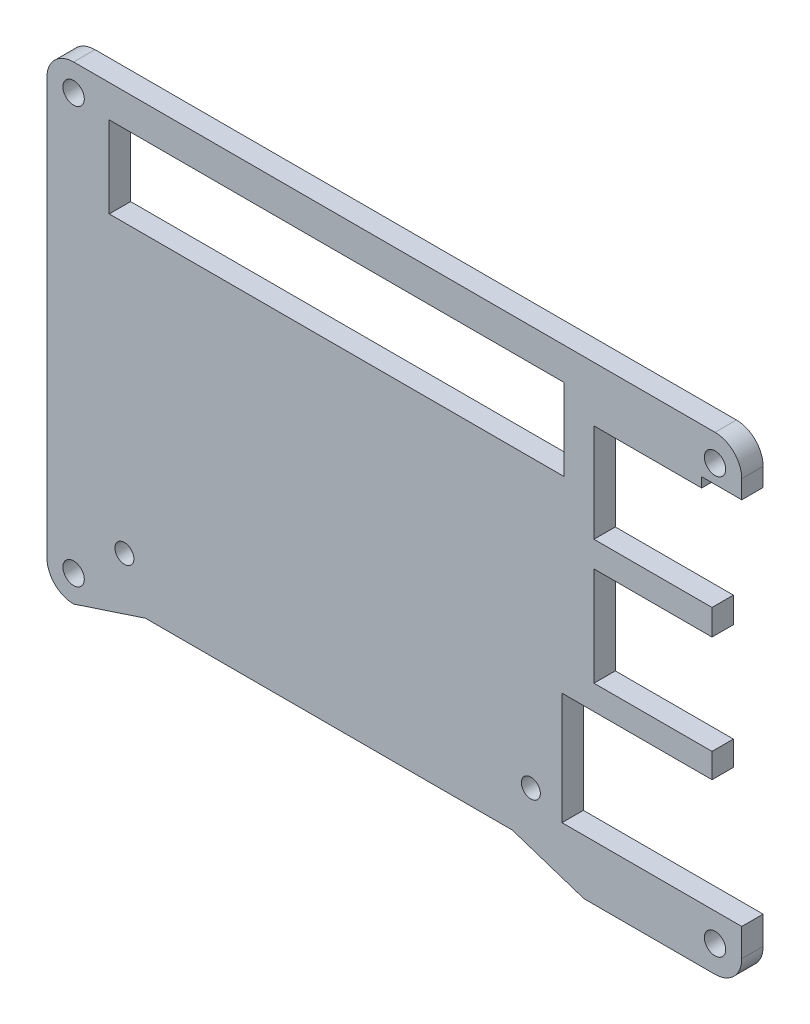
SolidWorks part; units mm, degrees
ref_plane "Front Plane" through (0, 0, 0) normal (0, 0, 1) x (1, 0, 0)
ref_plane "Top Plane" through (0, 0, 0) normal (0, 1, 0) x (1, 0, 0)
ref_plane "Right Plane" through (0, 0, 0) normal (1, 0, 0) x (0, 0, -1)
sketch "Sketch1" plane through (0, 0, 0) normal (0, 0, 1) x (1, 0, 0)
  line L1 (61.2149, 24.0683) -> (61.2149, 26.6839) construction
  line L2 (57.4049, 30.5077) -> (-34.0849, 30.5077) construction
  line L5 (56.975, 4.9979) -> (56.975, 8.6582) construction
  line L9 (56.975, -12.628) -> (56.975, -9.1218) construction
  line L10 (35.575, -12.628) -> (56.975, -12.628) construction
  line L11 (35.575, -28.6278) -> (35.575, -12.628) construction
  line L12 (61.2149, -28.6278) -> (35.575, -28.6278) construction
  line L13 (61.2149, -32.6134) -> (61.2149, -28.6278) construction
  line L14 (38.7143, -36.451) -> (57.405, -36.451) construction
  line L15 (28.4743, -33.0844) -> (38.7143, -36.451) construction
  line L16 (-23.8449, -33.0844) -> (28.4743, -33.0844) construction
  line L17 (-34.0849, -36.451) -> (-23.8449, -33.0844) construction
  line L18 (-37.8949, 26.6977) -> (-37.8949, -32.641) construction
  line L19 (61.2149, 24.0683) -> (40.1348, 24.0683)
  line L20 (61.2149, 24.0683) -> (61.2149, 26.6839)
  line L21 (57.4049, 30.5077) -> (-34.0849, 30.5077)
  line L22 (40.1348, 24.0683) -> (40.1348, 8.6582)
  line L23 (40.1348, 8.6582) -> (56.975, 8.6582)
  line L24 (56.975, 4.9979) -> (56.975, 8.6582)
  line L25 (56.975, 4.9979) -> (40.1348, 4.9979)
  line L26 (40.1348, 4.9979) -> (40.1348, -9.1218)
  line L27 (40.1348, -9.1218) -> (56.975, -9.1218)
  line L28 (56.975, -12.628) -> (56.975, -9.1218)
  line L29 (35.575, -12.628) -> (56.975, -12.628)
  line L30 (35.575, -28.6278) -> (35.575, -12.628)
  line L31 (61.2149, -28.6278) -> (35.575, -28.6278)
  line L32 (61.2149, -32.6134) -> (61.2149, -28.6278)
  line L33 (38.7143, -36.451) -> (57.405, -36.451)
  line L34 (28.4743, -33.0844) -> (38.7143, -36.451)
  line L35 (-23.8449, -33.0844) -> (28.4743, -33.0844)
  line L36 (-34.0849, -36.451) -> (-23.8449, -33.0844)
  line L37 (-37.8949, 26.6977) -> (-37.8949, -32.641)
  line L38 (-23.4169, -23.6989) -> (-23.4169, 9.8012) construction
  line L39 (-29.0049, 25.897) -> (31.6883, 25.897)
  line L40 (-29.0049, 25.897) -> (-29.0049, 18.087)
  line L41 (-29.0049, 18.087) -> (31.6883, 18.087)
  line L42 (31.6883, 25.897) -> (31.6883, 18.087)
  line L43 (-29.0049, 9.8012) -> (-23.4169, 9.8012)
  line L44 (-29.0049, 9.8012) -> (-29.0049, -13.5668)
  line L45 (-29.0049, -13.5668) -> (-23.4169, -13.5668)
  line L46 (-23.4169, 9.8012) -> (-23.4169, -13.5668)
  line L47 (-29.0049, 9.2932) -> (-23.4169, 9.2932)
  line L50 (13.845, -8.3602) -> (19.2484, -8.3602)
  line L51 (13.845, -8.3602) -> (13.845, -30.9668)
  line L52 (13.845, -30.9668) -> (19.2484, -30.9668)
  line L53 (19.2484, -8.3602) -> (19.2484, -30.9668)
  arc A0 (61.2149, 26.6839) -> (57.4049, 30.5077) centre (57.4049, 26.6977) ccw construction
  arc A2 (57.405, -36.451) -> (61.2149, -32.6134) centre (57.405, -32.641) ccw construction
  arc A3 (-37.8949, -32.641) -> (-34.0849, -36.451) centre (-34.0849, -32.641) ccw construction
  arc A4 (-34.0849, 30.5077) -> (-37.8949, 26.6977) centre (-34.0849, 26.6977) ccw construction
  arc A7 (61.2149, 26.6839) -> (57.4049, 30.5077) centre (57.4049, 26.6977) ccw
  circle A8 centre (57.405, -32.641) radius 1.524
  arc A9 (57.405, -36.451) -> (61.2149, -32.6134) centre (57.405, -32.641) ccw
  arc A10 (-37.8949, -32.641) -> (-34.0849, -36.451) centre (-34.0849, -32.641) ccw
  arc A11 (-34.0849, 30.5077) -> (-37.8949, 26.6977) centre (-34.0849, 26.6977) ccw
  circle A12 centre (-34.0849, -32.641) radius 1.524
  circle A13 centre (-34.0849, 26.6977) radius 1.524
  circle A15 centre (57.4049, 26.6977) radius 1.524
  dimension "D5" = 3.048
  dimension "D1" = 23.368
  dimension "D2" = 0.508
  dimension "D3" = 16.8402
  dimension "D4" = 16.8402
extrude "Boss-Extrude1" add sketch "Sketch1" along normal blind 3.048 contours L21 A11 L37 A10 L36 L35 L34 L33 A9 L32 L31 L30 L29 L28 L24 L20 A7 L50 L53 L52 L51 L39 L42 L41 L40 L43 L46 L45 L44 A12 region at (5.2192, -3.5296, 0)
sketch "Sketch2" plane through (0, 0, 3.048) normal (0, 0, 1) x (1, 0, 0)
  line L2 (-37.8949, 26.6977) -> (-37.8949, -32.641) construction
  line L5 (57.4049, 30.5077) -> (-34.0849, 30.5077) construction
  line L6 (-10.2851, -8.9639) -> (-10.2851, 8.0033) construction
  line L7 (-8.7865, -10.4625) -> (8.1807, -10.4625) construction
  line L8 (9.6793, -8.9639) -> (9.6793, 8.0033) construction
  line L9 (8.1807, 9.5019) -> (-8.7865, 9.5019) construction
  line L10 (-10.2851, -10.4625) -> (9.6793, 9.5019) construction
  circle A0 centre (-0.3029, -0.4803) radius 10.922
  circle A1 centre (-10.2851, -10.4625) radius 1.4986
  circle A2 centre (-10.2851, 9.5019) radius 1.4986
  circle A3 centre (9.6793, -10.4625) radius 1.4986
  circle A4 centre (9.6793, 9.5019) radius 1.4986
  dimension "D1" = 26.67
  dimension "D2" = 20.066
  dimension "D3" = 21.844
  dimension "D4" = 16.9672
  dimension "D5" = 2.9972
extrude "Cut-Extrude1" cut sketch "Sketch2" against normal through all
sketch "Sketch3" plane through (0, 0, 3.048) normal (0, 0, 1) x (1, 0, 0)
  line L0 (13.845, -30.9668) -> (19.2484, -30.9668) construction
  line L1 (-29.0049, 25.897) -> (31.6883, 25.897)
  line L2 (-29.0049, 25.897) -> (-29.0049, -30.9668)
  line L3 (-29.0049, -30.9668) -> (31.6883, -30.9668)
  line L4 (31.6883, 25.897) -> (31.6883, -30.9668)
  line L5 (31.6883, 25.897) -> (31.6883, 18.087) construction
extrude "Boss-Extrude2" add sketch "Sketch3" against normal up to vertex (3.048 mm away) up to point (-29.0049, 25.897, 0)
sketch "Sketch4" [suppressed] plane through (0, 0, 3.048) normal (0, 0, 1) x (1, 0, 0)
  circle A0 centre (-34.0849, -32.641) radius 1.524
  circle A1 centre (57.405, -32.641) radius 1.524
  circle A2 centre (-34.0849, -32.641) radius 1.524
  circle A3 centre (-34.0849, 26.6977) radius 1.524
  circle A4 centre (57.4049, 26.6977) radius 1.524
  dimension "D1" = 3.048
extrude "Cut-Extrude2" [suppressed] cut sketch "Sketch4" against normal through all
sketch "Sketch5" plane through (0, 0, 3.048) normal (0, 0, 1) x (1, 0, 0)
  line L1 (-29.0049, 25.897) -> (35.88, 25.897)
  line L2 (-29.0049, 25.897) -> (-29.0049, 14.277)
  line L3 (-29.0049, 14.277) -> (35.88, 14.277)
  line L4 (35.88, 25.897) -> (35.88, 14.277)
  line L19 (57.4049, 30.5077) -> (-34.0849, 30.5077)
  line L20 (-37.8949, 26.6977) -> (-37.8949, -32.641)
  line L21 (-34.0849, -36.451) -> (-23.8449, -33.0844)
  line L22 (-23.8449, -33.0844) -> (28.4743, -33.0844)
  line L23 (28.4743, -33.0844) -> (38.7143, -36.451)
  line L24 (38.7143, -36.451) -> (57.405, -36.451)
  line L25 (61.2149, -32.6134) -> (61.2149, -28.6278)
  line L26 (61.2149, -28.6278) -> (35.575, -28.6278)
  line L27 (35.575, -28.6278) -> (35.575, -12.628)
  line L28 (35.575, -12.628) -> (56.975, -12.628)
  line L29 (56.975, -12.628) -> (56.975, -9.1218)
  line L30 (56.975, -9.1218) -> (40.1348, -9.1218)
  line L31 (40.1348, -9.1218) -> (40.1348, 4.9979)
  line L32 (40.1348, 4.9979) -> (56.975, 4.9979)
  line L33 (56.975, 4.9979) -> (56.975, 8.6582)
  line L34 (56.975, 8.6582) -> (40.1348, 8.6582)
  line L35 (40.1348, 8.6582) -> (40.1348, 24.0683)
  line L36 (40.1348, 24.0683) -> (61.2149, 24.0683)
  line L37 (61.2149, 24.0683) -> (61.2149, 26.6839)
  line L38 (57.4049, 30.5077) -> (-34.0849, 30.5077)
  line L39 (-37.8949, 26.6977) -> (-37.8949, -32.641)
  line L40 (-34.0849, -36.451) -> (-23.8449, -33.0844)
  line L41 (-23.8449, -33.0844) -> (28.4743, -33.0844)
  line L42 (28.4743, -33.0844) -> (38.7143, -36.451)
  line L43 (38.7143, -36.451) -> (57.405, -36.451)
  line L44 (61.2149, -32.6134) -> (61.2149, -28.6278)
  line L45 (61.2149, -28.6278) -> (35.575, -28.6278)
  line L46 (35.575, -28.6278) -> (35.575, -12.628)
  line L47 (35.575, -12.628) -> (56.975, -12.628)
  line L48 (56.975, -12.628) -> (56.975, -9.1218)
  line L49 (56.975, -9.1218) -> (40.1348, -9.1218)
  line L50 (40.1348, -9.1218) -> (40.1348, 4.9979)
  line L51 (40.1348, 4.9979) -> (56.975, 4.9979)
  line L52 (56.975, 4.9979) -> (56.975, 8.6582)
  line L53 (56.975, 8.6582) -> (40.1348, 8.6582)
  line L54 (40.1348, 8.6582) -> (40.1348, 24.0683)
  line L55 (40.1348, 24.0683) -> (61.2149, 24.0683)
  line L56 (61.2149, 24.0683) -> (61.2149, 26.6839)
  circle A0 centre (-26.8395, -26.5725) radius 2.7305
  circle A1 centre (31.136, -26.5725) radius 2.7305
  arc A4 (-34.0849, 30.5077) -> (-37.8949, 26.6977) centre (-34.0849, 26.6977) ccw
  arc A5 (-37.8949, -32.641) -> (-34.0849, -36.451) centre (-34.0849, -32.641) ccw
  arc A6 (57.405, -36.451) -> (61.2149, -32.6134) centre (57.405, -32.641) ccw
  arc A7 (61.2149, 26.6839) -> (57.4049, 30.5077) centre (57.4049, 26.6977) ccw
  arc A8 (-34.0849, 30.5077) -> (-37.8949, 26.6977) centre (-34.0849, 26.6977) ccw
  arc A9 (-37.8949, -32.641) -> (-34.0849, -36.451) centre (-34.0849, -32.641) ccw
  arc A10 (57.405, -36.451) -> (61.2149, -32.6134) centre (57.405, -32.641) ccw
  arc A11 (61.2149, 26.6839) -> (57.4049, 30.5077) centre (57.4049, 26.6977) ccw
  dimension "D1" = 0
extrude "Cut-Extrude3" cut sketch "Sketch5" against normal through all contours L4 L1 L2 L3 | A0 | A1 region at (3.4376, 20.087, 3.048) region at (-26.8395, -26.5725, 3.048) region at (31.136, -26.5725, 3.048)
sketch "Sketch6" plane through (0, 0, 3.048) normal (0, 0, 1) x (1, 0, 0)
  circle A0 centre (-26.8395, -26.5725) radius 1.3525
  circle A1 centre (31.136, -26.5725) radius 1.3525
  circle A2 centre (-26.8395, -26.5725) radius 2.7305
  circle A3 centre (31.136, -26.5725) radius 2.7305
  dimension "D1" = 2.7051
  dimension "D2" = 5.461
extrude "Boss-Extrude3" add sketch "Sketch6" against normal blind 3.048
sketch "Sketch7" plane through (0, 0, 3.048) normal (0, 0, 1) x (1, 0, 0)
  line L1 (55.4999, 22.6713) -> (40.1348, 22.6713)
  line L2 (55.4999, 22.6713) -> (55.4999, 24.0683)
  line L3 (55.4999, 24.0683) -> (40.1348, 24.0683)
  line L4 (40.1348, 22.6713) -> (40.1348, 24.0683)
  dimension "D1" = 1.397
  dimension "D2" = 15.3651
extrude "Boss-Extrude4" add sketch "Sketch7" against normal blind 3.048
